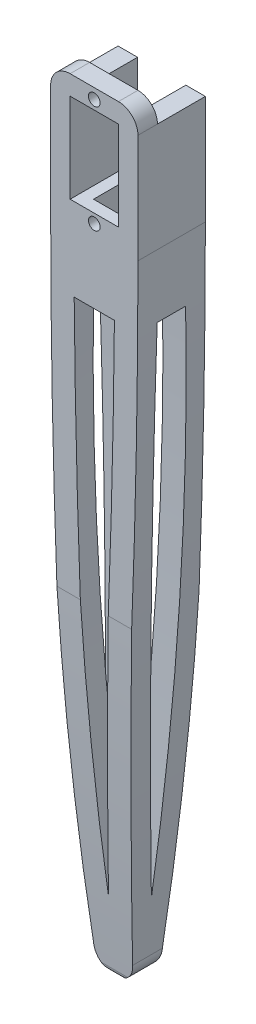
SolidWorks part; units mm, degrees
ref_plane "Front Plane" through (0, 0, 0) normal (0, 0, 1) x (1, 0, 0)
ref_plane "Top Plane" through (0, 0, 0) normal (0, 1, 0) x (1, 0, 0)
ref_plane "Right Plane" through (0, 0, 0) normal (1, 0, 0) x (0, 0, -1)
sketch "Sketch1" plane through (0, 0, 0) normal (0, 0, 1) x (1, 0, 0)
  line L0 (0, -16.45) -> (0, -173.55) construction
  line L1 (-6.2, 16.45) -> (6.2, 16.45)
  line L2 (-11.2, 11.45) -> (-11.2, -16.45)
  line L4 (11.2, 11.45) -> (11.2, -16.45)
  line L5 (-11.2, 16.45) -> (11.2, -16.45) construction
  line L6 (-11.2, -16.45) -> (11.2, 16.45) construction
  arc A1 (-5, -178.55) -> (5, -178.55) centre (0, -178.55) ccw
  arc A2 (-11.2, -16.45) -> (-5, -178.55) centre (2110.9653, -16.45) ccw
  arc A3 (11.2, -16.45) -> (5, -178.55) centre (-2110.9653, -16.45) cw
  arc A4 (11.2, 11.45) -> (6.2, 16.45) centre (6.2, 11.45) ccw
  arc A5 (-6.2, 16.45) -> (-11.2, 11.45) centre (-6.2, 11.45) ccw
  point P0 (0, 0)
  dimension "D4" = 5
  dimension "D1" = 32.9
  dimension "D2" = 22.4
  dimension "D3" = 162.1
extrude "Boss-Extrude2" add sketch "Sketch1" along normal blind 5
sketch "Sketch4" plane through (0, 0, 5) normal (0, 0, 1) x (1, 0, 0)
  line L1 (-6.2, 11.45) -> (6.2, 11.45)
  line L2 (-6.2, 11.45) -> (-6.2, -11.45)
  line L3 (-6.2, -11.45) -> (6.2, -11.45)
  line L4 (6.2, 11.45) -> (6.2, -11.45)
  line L5 (-6.2, 11.45) -> (6.2, -11.45) construction
  line L6 (-6.2, -11.45) -> (6.2, 11.45) construction
  point P0 (0, 0)
  dimension "D1" = 22.9
  dimension "D2" = 12.4
extrude "Cut-Extrude1" cut sketch "Sketch4" against normal blind 5
sketch "Sketch5" plane through (0, 0, 5) normal (0, 0, 1) x (1, 0, 0)
  line L0 (0, 0) -> (0, 13.8) construction
  line L1 (0, 0) -> (0, -13.8) construction
  circle A0 centre (0, 13.8) radius 1.5
  circle A1 centre (0, -13.8) radius 1.5
  dimension "D1" = 13.8
  dimension "D2" = 13.8
extrude "Cut-Extrude2" cut sketch "Sketch5" against normal blind 5
sketch3d "3DSketch1"
  line L6 (-5.1604, -32.6864, 5) -> (5.1604, -32.6864, 5)
  spline S2 degree 5 poles (-5.1604, -32.6864, 5) (-5.1261, -37.5289, 5) (-5.0708, -42.3713, 5) (-4.9981, -47.2135, 5) (-4.7659, -60.1446, 5) (-4.4569, -73.0738, 5) (-4.2293, -81.1606, 5) (-3.6967, -97.3316, 5) (-2.9925, -113.496, 5) (-2.6018, -121.5766, 5) (-1.8933, -135.0415, 5) (-1.1015, -148.5022, 5) (-0.7667, -153.8853, 5) (-0.4048, -159.3358, 5) (-0.0148, -164.7842, 5) (-0.0099, -164.8531, 5) (-0.0049, -164.922, 5) (0, -164.9909, 5) knots 0.10922 0.10922 0.10922 0.10922 0.10922 0.10922 0.272094 0.272094 0.272094 0.544187 0.544187 0.544187 0.816281 0.816281 0.816281 0.997676 0.997676 0.997676 1 1 1 1 1 1
  spline S3 degree 5 poles (0, -164.9909, 5) (0.0049, -164.922, 5) (0.0099, -164.8531, 5) (0.0148, -164.7842, 5) (0.4048, -159.3358, 5) (0.7667, -153.8853, 5) (1.1015, -148.5022, 5) (1.8933, -135.0415, 5) (2.6018, -121.5766, 5) (2.9925, -113.496, 5) (3.6967, -97.3316, 5) (4.2293, -81.1606, 5) (4.4569, -73.0738, 5) (4.7659, -60.1446, 5) (4.9981, -47.2135, 5) (5.0708, -42.3713, 5) (5.1261, -37.5289, 5) (5.1604, -32.6864, 5) knots 0 0 0 0 0 0 0.002324 0.002324 0.002324 0.183719 0.183719 0.183719 0.455813 0.455813 0.455813 0.727906 0.727906 0.727906 0.89078 0.89078 0.89078 0.89078 0.89078 0.89078
extrude "Cut-Extrude3" cut sketch "3DSketch1" along direction (0, 0, -1) on the side against the normal blind 5
sketch "Sketch6" plane through (0, 0, 0) normal (0, 0, -1) x (-1, 0, 0)
  line L0 (0, 0) -> (-11.2, 0) construction
  line L1 (-11.2, -16.45) -> (-11.2, 11.45) construction
  line L2 (0, 0) -> (11.2, 0) construction
  line L3 (11.2, 11.45) -> (11.2, -16.45) construction
  line L4 (-11.2, 3.2511) -> (-6.2, 3.2511) construction
  line L5 (-6.2, -11.45) -> (-6.2, 11.45) construction
  line L6 (-8.7, 3.2511) -> (-8.7, 0) construction
  line L7 (6.2, 3.2511) -> (11.2, 3.2511) construction
  line L8 (6.2, 11.45) -> (6.2, -11.45) construction
  line L9 (8.7, 3.2511) -> (8.7, 0) construction
  line L11 (-11.2, 11.45) -> (-6.2, 11.45)
  line L12 (-11.2, 11.45) -> (-11.2, -11.45)
  line L13 (-11.2, -11.45) -> (-6.2, -11.45)
  line L14 (-6.2, 11.45) -> (-6.2, -11.45)
  line L15 (-11.2, 11.45) -> (-6.2, -11.45) construction
  line L16 (-11.2, -11.45) -> (-6.2, 11.45) construction
  line L17 (6.2, 11.45) -> (11.2, 11.45)
  line L18 (6.2, 11.45) -> (6.2, -11.45)
  line L19 (6.2, -11.45) -> (11.2, -11.45)
  line L20 (11.2, 11.45) -> (11.2, -11.45)
  line L21 (6.2, 11.45) -> (11.2, -11.45) construction
  line L22 (6.2, -11.45) -> (11.2, 11.45) construction
  dimension "D1" = 22.9
  dimension "D2" = 22.9
extrude "Boss-Extrude3" add sketch "Sketch6" along normal blind 12.3
sketch "Sketch7" plane through (0, 0, -12.3) normal (0, 0, -1) x (-1, 0, 0)
  circle A0 centre (-8.6658, 0) radius 1.5
  circle A1 centre (8.8805, 0) radius 1.5
extrude "Cut-Extrude4" cut sketch "Sketch7" against normal blind 5
sketch "Sketch8" plane through (0, 0, 0) normal (0, 0, -1) x (-1, 0, 0)
  line L15 (11.2, -16.45) -> (11.2, -11.45)
  line L16 (11.2, -11.45) -> (6.2, -11.45)
  line L17 (6.2, -11.45) -> (-6.2, -11.45)
  line L18 (-6.2, -11.45) -> (-11.2, -11.45)
  line L19 (-11.2, -11.45) -> (-11.2, -16.45)
  line L20 (11.2, -16.45) -> (11.2, -11.45)
  line L21 (11.2, -11.45) -> (6.2, -11.45)
  line L22 (6.2, -11.45) -> (-6.2, -11.45)
  line L23 (-6.2, -11.45) -> (-11.2, -11.45)
  line L24 (-11.2, -11.45) -> (-11.2, -16.45)
  arc A9 (-11.2, -16.45) -> (-5, -178.55) centre (2110.9653, -16.45) ccw
  arc A10 (-5, -178.55) -> (5, -178.55) centre (0, -178.55) ccw
  arc A11 (5, -178.55) -> (11.2, -16.45) centre (-2110.9653, -16.45) ccw
  arc A12 (-11.2, -16.45) -> (-5, -178.55) centre (2110.9653, -16.45) ccw
  arc A13 (-5, -178.55) -> (5, -178.55) centre (0, -178.55) ccw
  arc A14 (5, -178.55) -> (11.2, -16.45) centre (-2110.9653, -16.45) ccw
  dimension "D1" = 0
extrude "Boss-Extrude4" add sketch "Sketch8" along normal up to surface (12.3 mm away) up to face at (7.1658, 0, -12.3)
sketch "Sketch10" plane through (0, 0, 0) normal (0, 0, 1) x (1, 0, 0)
  line L2 (5.1604, -32.6864) -> (-5.1604, -32.6864)
  line L3 (5.1604, -32.6864) -> (-5.1604, -32.6864)
  spline S4 degree 5 poles (3737.3345, 1021.9413) (1530.6076, 831.7399) (405.6632, 622.0723) (9.8674, 399.6215) (-10.0977, 162.9613) (-4.4569, -73.0738) (-4.2293, -81.1606) (-3.6967, -97.3316) (-2.9925, -113.496) (-2.6018, -121.5766) (-1.8933, -135.0415) (-1.1015, -148.5022) (-0.7667, -153.8853) (8.9939, -300.8625) (39.1089, -446.3258) (-244.3565, -609.7033) (-1173.9892, -820.4372) (3001.0885, 804.2975) knots -7.396562 -7.396562 -7.396562 -7.396562 -7.396562 -7.396562 0.272094 0.272094 0.272094 0.544187 0.544187 0.544187 0.816281 0.816281 0.816281 0.997676 0.997676 0.997676 5.770453 5.770453 5.770453 5.770453 5.770453 5.770453 only from (-5.1604, -32.6864) to (0, -164.9909)
  spline S5 degree 5 poles (-3577.3867, -1342.699) (603.7313, -672.1525) (115.8024, -520.199) (-28.9051, -393.7894) (-7.2329, -274.3458) (0.7667, -153.8853) (1.1015, -148.5022) (1.8933, -135.0415) (2.6018, -121.5766) (2.9925, -113.496) (3.6967, -97.3316) (4.2293, -81.1606) (4.4569, -73.0738) (10.0977, 162.9618) (-9.8674, 399.6224) (-405.6655, 622.0735) (-1530.6163, 831.7415) (-3737.3555, 1021.9431) knots -3.876652 -3.876652 -3.876652 -3.876652 -3.876652 -3.876652 0.002324 0.002324 0.002324 0.183719 0.183719 0.183719 0.455813 0.455813 0.455813 0.727906 0.727906 0.727906 8.396576 8.396576 8.396576 8.396576 8.396576 8.396576 only from (0, -164.9909) to (5.1604, -32.6864)
  spline S6 degree 5 poles (-5.1604, -32.6864) (-5.1261, -37.5289) (-5.0708, -42.3713) (-4.9981, -47.2135) (-4.7659, -60.1446) (-4.4569, -73.0738) (-4.2293, -81.1606) (-3.6967, -97.3316) (-2.9925, -113.496) (-2.6018, -121.5766) (-1.8933, -135.0415) (-1.1015, -148.5022) (-0.7667, -153.8853) (-0.4048, -159.3358) (-0.0148, -164.7842) (-0.0099, -164.8531) (-0.0049, -164.922) (0, -164.9909) knots 0.10922 0.10922 0.10922 0.10922 0.10922 0.10922 0.272094 0.272094 0.272094 0.544187 0.544187 0.544187 0.816281 0.816281 0.816281 0.997676 0.997676 0.997676 1 1 1 1 1 1
  spline S7 degree 5 poles (0, -164.9909) (0.0049, -164.922) (0.0099, -164.8531) (0.0148, -164.7842) (0.4048, -159.3358) (0.7667, -153.8853) (1.1015, -148.5022) (1.8933, -135.0415) (2.6018, -121.5766) (2.9925, -113.496) (3.6967, -97.3316) (4.2293, -81.1606) (4.4569, -73.0738) (4.7659, -60.1446) (4.9981, -47.2135) (5.0708, -42.3713) (5.1261, -37.5289) (5.1604, -32.6864) knots 0 0 0 0 0 0 0.002324 0.002324 0.002324 0.183719 0.183719 0.183719 0.455813 0.455813 0.455813 0.727906 0.727906 0.727906 0.89078 0.89078 0.89078 0.89078 0.89078 0.89078
  dimension "D1" = 0
extrude "Cut-Extrude5" cut sketch "Sketch10" against normal blind 121
sketch "Sketch12" plane through (0, 0, 0) normal (1, 0, 0) x (0, 0, -1)
  line L2 (3.65, -183.55) -> (3.65, -164.9909) construction
  line L3 (-5, -183.55) -> (12.3, -183.55) construction
  line L6 (0, -32.6864) -> (7.3, -32.6864)
  line L7 (3.65, -32.6864) -> (3.65, -164.9909) construction
  arc A0 (0, -32.6864) -> (3.65, -164.9909) centre (1196.4285, -65.8821) ccw
  arc A1 (7.3, -32.6864) -> (3.65, -164.9909) centre (-1189.1285, -65.8821) cw
extrude "Cut-Extrude7" cut sketch "Sketch12" against normal through all
sketch "Sketch14" plane through (0, 0, 0) normal (1, 0, 0) x (0, 0, -1)
  line L0 (7.3, -32.6864) -> (0, -32.6864)
  arc A0 (7.3, -32.6864) -> (3.65, -164.9909) centre (-1189.1285, -65.8821) cw
  arc A1 (0, -32.6864) -> (3.65, -164.9909) centre (1196.4285, -65.8821) ccw
extrude "Cut-Extrude8" cut sketch "Sketch14" along normal blind 121
sketch "Sketch15" plane through (0, 0, 0) normal (1, 0, 0) x (0, 0, -1)
  line L6 (12.3019, -32.6864) -> (24.1567, -32.6864)
  line L7 (24.1567, -32.6864) -> (24.1567, -183.55)
  line L8 (24.1567, -183.55) -> (5.6261, -183.55)
  line L9 (-5.0019, -32.6864) -> (-15.6441, -32.6864)
  line L10 (-15.6441, -32.6864) -> (-15.6441, -183.55)
  line L11 (1.6739, -183.55) -> (-15.6441, -183.55)
  arc A2 (12.3019, -32.6864) -> (7.1191, -182.1952) centre (-1189.1285, -65.8821) cw
  arc A3 (-5.0019, -32.6864) -> (0.1809, -182.1952) centre (1196.4285, -65.8821) ccw
  arc A6 (5.6261, -183.55) -> (7.1191, -182.1952) centre (5.6261, -182.05) ccw
  arc A7 (1.6739, -183.55) -> (0.1809, -182.1952) centre (1.6739, -182.05) cw
  dimension "D2" = 1.5
extrude "Cut-Extrude12" cut sketch "Sketch15" against normal mid plane 121
sketch "Sketch16" plane through (0, -11.45, 0) normal (0, 1, 0) x (1, 0, 0)
  line L8 (-3.2, -2) -> (3.2, -2)
  line L9 (3.2, -2) -> (3.2, 9.3)
  line L10 (3.2, 9.3) -> (-3.2, 9.3)
  line L11 (-3.2, 9.3) -> (-3.2, -2)
  line L12 (-3.2, -2) -> (3.2, -2)
  line L13 (3.2, -2) -> (3.2, 9.3)
  line L14 (3.2, 9.3) -> (-3.2, 9.3)
  line L15 (-3.2, 9.3) -> (-3.2, -2)
  dimension "D1" = 3
extrude "Cut-Extrude13" cut sketch "Sketch16" against normal up to surface (21.2364 mm away) contours L12 L13 L14 L15
